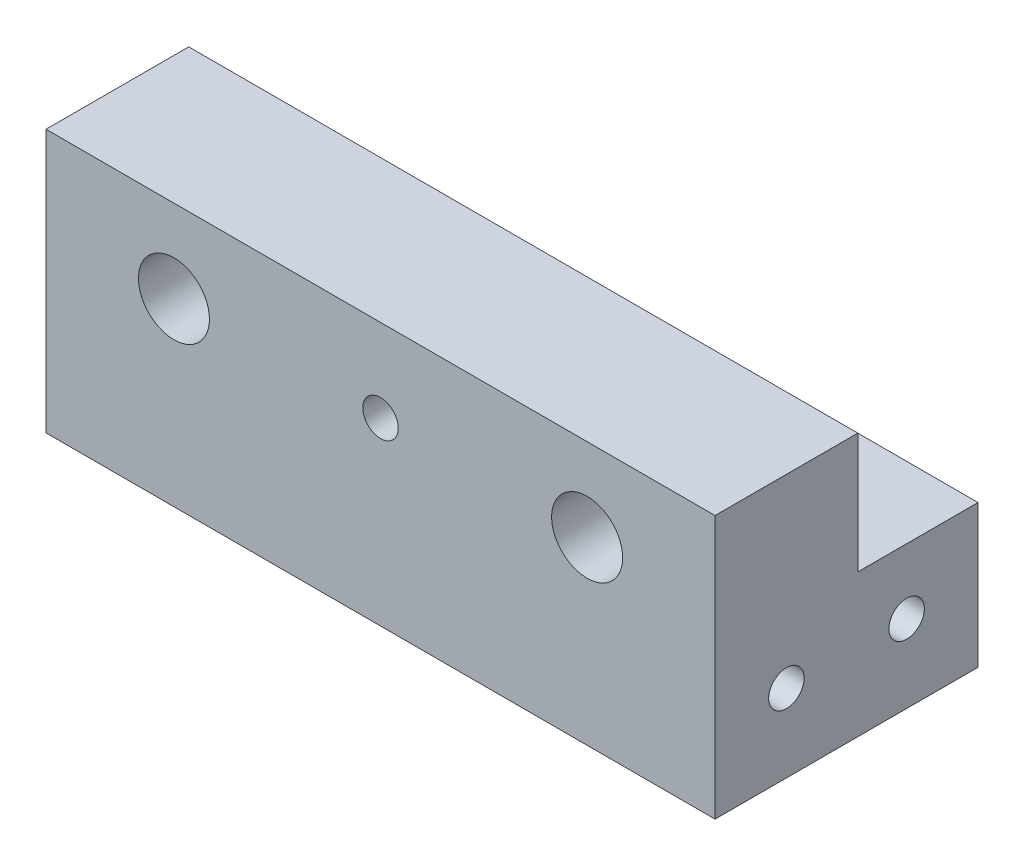
SolidWorks part; units mm, degrees
material "6061-T6 (SS)"
ref_plane "X-Y Datum" through (0, 0, 0) normal (0, 0, 1) x (1, 0, 0)
ref_plane "X-Z Datum" through (0, 0, 0) normal (0, 1, 0) x (1, 0, 0)
ref_plane "Y-Z Datum" through (0, 0, 0) normal (1, 0, 0) x (0, 0, -1)
sketch "Sketch1" plane through (0, 0, 0) normal (0, 0, 1) x (1, 0, 0)
  line L1 (-28.275, 11.1125) -> (28.275, 11.1125)
  line L2 (-28.275, 11.1125) -> (-28.275, -11.1125)
  line L3 (-28.275, -11.1125) -> (28.275, -11.1125)
  line L4 (28.275, 11.1125) -> (28.275, -11.1125)
  line L5 (-28.275, 11.1125) -> (28.275, -11.1125) construction
  line L6 (-28.275, -11.1125) -> (28.275, 11.1125) construction
  point P0 (0, 0)
  dimension "D1" = 56.55
  dimension "D2" = 22.225
extrude "Boss-Extrude1" add sketch "Sketch1" along normal blind 22.225 contours L2 L3 L4 L1
sketch "Sketch2" plane through (0, 0, 22.225) normal (0, 0, 1) x (1, 0, 0)
  line L0 (-23.5453, 4.1125) -> (31.0951, 4.1125) construction
  line L1 (0, 11.1125) -> (0, -11.1125) construction
  line L2 (-28.275, 11.1125) -> (28.275, 11.1125) construction
  line L3 (-17.4625, 4.1125) -> (17.4625, 4.1125) construction
  line L4 (-28.275, -11.1125) -> (28.275, -11.1125) construction
  circle A0 centre (17.4625, 4.1125) radius 3
  circle A1 centre (-17.4625, 4.1125) radius 3
  circle A2 centre (0, 4.1125) radius 1.5
  point P10 (0, 4.1125)
  dimension "D1" = 6
  dimension "D4" = 3
  dimension "D2" = 34.925
  dimension "D3" = 7
extrude "Cut-Extrude1" cut sketch "Sketch2" against normal blind 10 contours A1 L0 L3 | L0 A1 L3 | L0 L3 A0 | L3 L0 A0 | A2 region at (17.4625, 4.1125, 22.225) region at (-17.4625, 4.1125, 22.225) region at (0, 4.1125, 22.225)
sketch "Sketch3" plane through (-28.275, 0, 0) normal (-1, 0, 0) x (0, 0, 1)
  line L0 (0, -4.5375) -> (22.225, -4.5375) construction
  line L1 (0, 11.1125) -> (0, -11.1125) construction
  line L2 (22.225, 184.8875) -> (22.225, -15.7125) construction
  line L3 (16.1925, -4.5375) -> (6.0325, -4.5375) construction
  line L4 (11.1125, 11.1125) -> (11.1125, -11.1125) construction
  line L5 (22.225, 11.1125) -> (0, 11.1125) construction
  line L6 (22.225, -11.1125) -> (0, -11.1125) construction
  line L7 (-277.475, -12.5375) -> (22.225, -12.5375) construction
  circle A0 centre (16.1925, -4.5375) radius 1.5
  circle A1 centre (6.0325, -4.5375) radius 1.5
  point P10 (11.1125, -4.5375)
  dimension "D1" = 3
  dimension "D2" = 10.16
  dimension "D3" = 8
extrude "Cut-Extrude2" cut sketch "Sketch3" against normal through all
sketch "Sketch4" plane through (-28.275, 0, 0) normal (-1, 0, 0) x (0, 0, 1)
  line L1 (0, 11.1125) -> (10.16, 11.1125)
  line L2 (0, 11.1125) -> (0, 0.9525)
  line L3 (0, 0.9525) -> (10.16, 0.9525)
  line L4 (10.16, 11.1125) -> (10.16, 0.9525)
  dimension "D1" = 10.16
  dimension "D2" = 10.16
extrude "Cut-Extrude3" cut sketch "Sketch4" against normal through all
